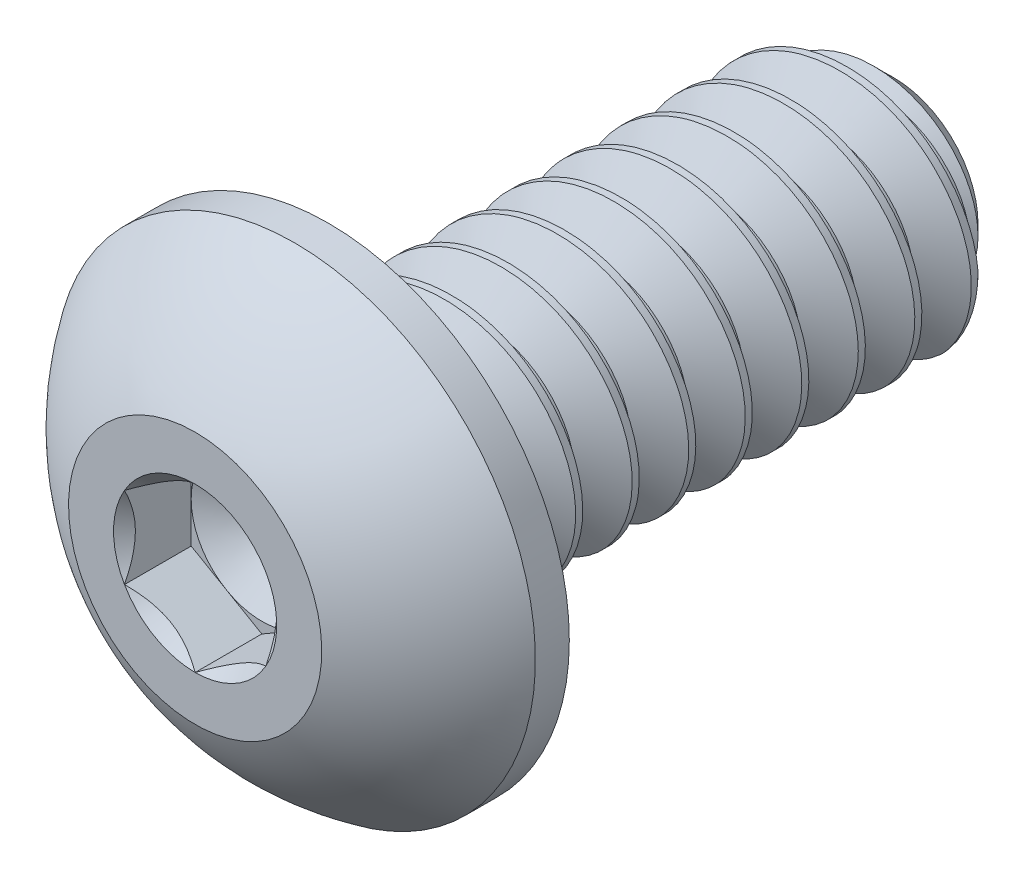
SolidWorks part; units mm, degrees
ref_plane "Front" through (0, 0, 0) normal (0, 0, 1) x (1, 0, 0)
ref_plane "Top" through (0, 0, 0) normal (0, 1, 0) x (1, 0, 0)
ref_plane "Right" through (0, 0, 0) normal (1, 0, 0) x (0, 0, -1)
sketch "Sketch1" plane through (0, 0, 0) normal (1, 0, 0) x (0, 0, -1)
  line L0 (0, 0) -> (-1.4986, 0) construction
  line L1 (0, 0) -> (6.35, 0)
  line L2 (0, 0) -> (0, 1.4224)
  line L3 (0, 1.4224) -> (6.35, 1.4224)
  line L4 (6.35, 0) -> (6.35, 1.4224)
  line L5 (0, -1.4224) -> (6.35, -1.4224) construction
  dimension "D1" = 6.35
  dimension "Thread Dia" = 2.8448
  dimension "Length" = 6.35
  dimension "Head Height" = 1.4986
revolve "Revolve1" add sketch "Sketch1" angle 360 about L0
ref_plane "Plane1" through (0, 0, 1.4986) normal (0, 0, 1) x (1, 0, 0)
chamfer "Chamfer1" distance 0.4763 angle 45 1 edges at (0, 1.4224, -6.35)
sketch "Sketch10" plane through (0, 0, 0) normal (1, 0, 0) x (0, 0, -1)
  line L0 (6.35, 1.4224) -> (6.9056, 1.4224)
  line L1 (6.9056, 1.4224) -> (6.6675, 1.01)
  line L2 (6.6675, 1.01) -> (6.5881, 1.01)
  line L3 (6.5881, 1.01) -> (6.35, 1.4224)
  line L4 (6.4691, 1.2162) -> (6.7866, 1.2162) construction
  dimension "D1" = 60
  dimension "D2" = 0.0794
  dimension "D3" = 0.3175
sketch "Sketch11" plane through (0, 0, -6.35) normal (0, 0, -1) x (-1, 0, 0)
  circle A1 centre (0, 0) radius 0.9461
  circle A2 centre (0, 0) radius 0.9461
  dimension "D1" = 0
curve "Helix/Spiral1" pitch 0.635 height 9.525 turns 15
sweep "Cut-Sweep1" cut profiles "Sketch10" path "Helix/Spiral1"
sketch "Sketch4" plane through (0, 0, 0) normal (0, 0, 1) x (1, 0, 0)
  circle A0 centre (0, 0) radius 2.7051
  dimension "Head Dia" = 5.4102
extrude "Extrude1" add sketch "Sketch4" along normal up to surface (1.4986 mm away) up to plane "Plane1"
sketch "Sketch9" plane through (0, 0, 0) normal (1, 0, 0) x (0, 0, -1)
  line L0 (0, 2.7051) -> (-0.381, 2.7051)
  line L1 (0, 2.7051) -> (0, 3.0861)
  line L2 (0, 3.0861) -> (-1.8796, 3.0861)
  line L3 (0, 0) -> (-1.4986, 0) construction
  line L4 (-1.8796, 3.0861) -> (-1.8796, 1.4224)
  line L5 (-1.8796, 1.4224) -> (-1.4986, 1.4224)
  line L6 (0, 0) -> (0, 1.4224) construction
  line L10 (0, 2.7051) -> (-1.4986, 2.7051) construction
  line L11 (0, 1.4224) -> (6.35, 1.4224) construction
  line L12 (-1.4986, 2.7051) -> (-1.4986, -2.7051) construction
  arc A0 (-1.4986, 1.4224) -> (-0.381, 2.7051) centre (1.4288, 0) cw
  dimension "Side Head Height" = 0.381
revolve "Cut-Revolve3" cut sketch "Sketch9" angle 360 about L3
sketch "Sketch6" plane through (0, 0, 1.4986) normal (0, 0, 1) x (1, 0, 0)
  line L1 (0, -0.9165) -> (0.7937, -0.4583)
  line L2 (0.7937, -0.4583) -> (0.7937, 0.4583)
  line L3 (0.7937, 0.4583) -> (0, 0.9165)
  line L4 (0, 0.9165) -> (-0.7938, 0.4583)
  line L5 (-0.7938, 0.4583) -> (-0.7938, -0.4583)
  line L6 (-0.7938, -0.4583) -> (0, -0.9165)
  circle A0 centre (0, 0) radius 0.7938 construction
  dimension "Hex" = 1.5875
extrude "Cut-Extrude1" cut sketch "Sketch6" against normal blind 0.7493
sketch "Sketch7" plane through (0, 0, 1.4986) normal (0, 0, 1) x (1, 0, 0)
  circle A0 centre (0, 0) radius 0.9165
extrude "Cut-Extrude4" cut sketch "Sketch7" against normal blind 0.7493 draft 45
sketch "Sketch8" plane through (0, 0, 0.7493) normal (0, 0, 1) x (1, 0, 0)
  circle A0 centre (0, 0) radius 0.7938 construction
  circle A1 centre (0, 0) radius 0.7938
extrude "Cut-Extrude5" cut sketch "Sketch8" against normal blind 0.2498 draft 60
sketch "Sketch12" plane through (0, 0, 0) normal (1, 0, 0) x (0, 0, -1)
  line L1 (0, -1.4224) -> (6.35, -1.4224) construction
  spline S0 degree 2 poles (5.8737, 0.013) (5.8319, 0.5945) (5.7944, 1.0058) (5.7415, 1.5865) (5.6885, 1.3739) (5.6356, 1.1614) (5.5827, 0.3681) (5.5298, -0.4251) (5.4769, -1.0058) (5.424, -1.5865) (5.371, -1.3739) (5.3181, -1.1614) (5.2652, -0.3681) (5.2123, 0.4251) (5.1594, 1.0058) (5.1065, 1.5865) (5.0535, 1.3739) (5.0006, 1.1614) (4.9477, 0.3681) (4.8948, -0.4251) (4.8419, -1.0058) (4.789, -1.5865) (4.736, -1.3739) (4.6831, -1.1614) (4.6302, -0.3681) (4.5773, 0.4251) (4.5244, 1.0058) (4.4715, 1.5865) (4.4185, 1.3739) (4.3656, 1.1614) (4.3127, 0.3681) (4.2598, -0.4251) (4.2069, -1.0058) (4.154, -1.5865) (4.101, -1.3739) (4.0481, -1.1614) (3.9952, -0.3681) (3.9423, 0.4251) (3.8894, 1.0058) (3.8365, 1.5865) (3.7835, 1.3739) (3.7306, 1.1614) (3.6777, 0.3681) (3.6248, -0.4251) (3.5719, -1.0058) (3.519, -1.5865) (3.466, -1.3739) (3.4131, -1.1614) (3.3602, -0.3681) (3.3073, 0.4251) (3.2544, 1.0058) (3.2015, 1.5865) (3.1485, 1.3739) (3.0956, 1.1614) (3.0427, 0.3681) (2.9898, -0.4251) (2.9369, -1.0058) (2.884, -1.5865) (2.831, -1.3739) (2.7781, -1.1614) (2.7252, -0.3681) (2.6723, 0.4251) (2.6194, 1.0058) (2.5665, 1.5865) (2.5135, 1.3739) (2.4606, 1.1614) (2.4077, 0.3681) (2.3548, -0.4251) (2.3019, -1.0058) (2.249, -1.5865) (2.196, -1.3739) (2.1431, -1.1614) (2.0902, -0.3681) (2.0373, 0.4251) (1.9844, 1.0058) (1.9315, 1.5865) (1.8785, 1.3739) (1.8256, 1.1614) (1.7727, 0.3681) (1.7198, -0.4251) (1.6669, -1.0058) (1.614, -1.5865) (1.561, -1.3739) (1.5081, -1.1614) (1.4552, -0.3681) (1.4023, 0.4251) (1.3494, 1.0058) (1.2965, 1.5865) (1.2435, 1.3739) (1.1906, 1.1614) (1.1377, 0.3681) (1.0848, -0.4251) (1.0319, -1.0058) (0.979, -1.5865) (0.926, -1.3739) (0.8731, -1.1614) (0.8202, -0.3681) (0.7673, 0.4251) (0.7144, 1.0058) (0.6615, 1.5865) (0.6085, 1.3739) (0.5556, 1.1614) (0.5027, 0.3681) (0.4498, -0.4251) (0.3969, -1.0058) (0.344, -1.5865) (0.291, -1.3739) (0.2381, -1.1614) (0.1852, -0.3681) (0.1323, 0.4251) (0.0794, 1.0058) (0.0419, 1.417) (0, 1.4223) knots 0.058478 0.058478 0.058478 0.066667 0.066667 0.077778 0.077778 0.088889 0.088889 0.1 0.1 0.111111 0.111111 0.122222 0.122222 0.133333 0.133333 0.144444 0.144444 0.155556 0.155556 0.166667 0.166667 0.177778 0.177778 0.188889 0.188889 0.2 0.2 0.211111 0.211111 0.222222 0.222222 0.233333 0.233333 0.244444 0.244444 0.255556 0.255556 0.266667 0.266667 0.277778 0.277778 0.288889 0.288889 0.3 0.3 0.311111 0.311111 0.322222 0.322222 0.333333 0.333333 0.344444 0.344444 0.355556 0.355556 0.366667 0.366667 0.377778 0.377778 0.388889 0.388889 0.4 0.4 0.411111 0.411111 0.422222 0.422222 0.433333 0.433333 0.444444 0.444444 0.455556 0.455556 0.466667 0.466667 0.477778 0.477778 0.488889 0.488889 0.5 0.5 0.511111 0.511111 0.522222 0.522222 0.533333 0.533333 0.544444 0.544444 0.555556 0.555556 0.566667 0.566667 0.577778 0.577778 0.588889 0.588889 0.6 0.6 0.611111 0.611111 0.622222 0.622222 0.633333 0.633333 0.644444 0.644444 0.655556 0.655556 0.666667 0.666667 0.674856 0.674856 0.674856 weights 0.948065 0.901259 1 0.866025 1 0.866025 1 0.866025 1 0.866025 1 0.866025 1 0.866025 1 0.866025 1 0.866025 1 0.866025 1 0.866025 1 0.866025 1 0.866025 1 0.866025 1 0.866025 1 0.866025 1 0.866025 1 0.866025 1 0.866025 1 0.866025 1 0.866025 1 0.866025 1 0.866025 1 0.866025 1 0.866025 1 0.866025 1 0.866025 1 0.866025 1 0.866025 1 0.866025 1 0.866025 1 0.866025 1 0.866025 1 0.866025 1 0.866025 1 0.866025 1 0.866025 1 0.866025 1 0.866025 1 0.866025 1 0.866025 1 0.866025 1 0.866025 1 0.866025 1 0.866025 1 0.866025 1 0.866025 1 0.866025 1 0.866025 1 0.866025 1 0.866025 1 0.866025 1 0.866025 1 0.866025 1 0.866025 1 0.901259 0.948065 construction
  point P0 (5.3966, -1.4224)
equation "\"D1@Cut-Extrude1\"=\"Head Height@Sketch1\"/2"
equation "\"D1@Cut-Extrude4\"=\"D1@Cut-Extrude1\""
equation "\"D1@Cut-Extrude5\"=\"D1@Cut-Extrude1\"/3"
equation "\"D3@Helix/Spiral1\" = \"Length@Sketch1\" + .125"
equation "\"D1@Chamfer1\" = \"D4@Helix/Spiral1\" * .75"
equation "\"D2@Sketch10\" = \"D4@Helix/Spiral1\" * .125"
equation "\"D3@Sketch10\" = \"D4@Helix/Spiral1\" * .5"
